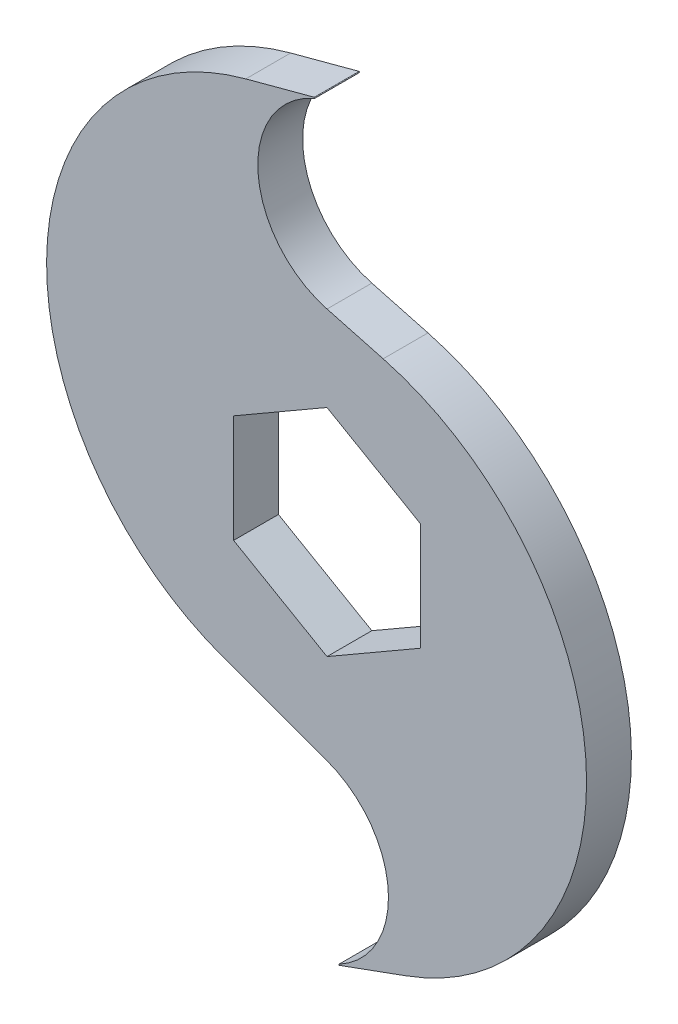
SolidWorks part; units mm, degrees
ref_plane "Front Plane" through (0, 0, 0) normal (0, 0, 1) x (1, 0, 0)
ref_plane "Top Plane" through (0, 0, 0) normal (0, 1, 0) x (1, 0, 0)
ref_plane "Right Plane" through (0, 0, 0) normal (1, 0, 0) x (0, 0, -1)
sketch "Sketch1" plane through (0, 0, 0) normal (0, 0, 1) x (1, 0, 0)
  line L0 (0, 50.8) -> (-11.0405, 47.8417)
  line L1 (0, 50.8) -> (0, 0) construction
  line L2 (0, -50.8) -> (10.7407, -46.8907)
  line L3 (0, 0) -> (0, -50.8) construction
  line L5 (0, 14.6647) -> (-12.7, 7.3323)
  line L6 (-12.7, 7.3323) -> (-12.7, -7.3323)
  line L7 (-12.7, -7.3323) -> (0, -14.6647)
  line L8 (0, -14.6647) -> (12.7, -7.3323)
  line L9 (12.7, -7.3323) -> (12.7, 7.3323)
  line L10 (12.7, 7.3323) -> (0, 14.6647)
  line L11 (0, 26.2655) -> (7.636, 24.2194)
  line L12 (0, -26.9318) -> (-14.0814, -21.8066)
  circle A0 centre (0, 0) radius 50.8 construction
  arc A1 (0, 50.8) -> (0, 26.2655) centre (3.287, 38.5327) ccw
  arc A3 (0, -50.8) -> (0, -26.9318) centre (-4.3437, -38.8659) ccw
  arc A4 (10.7407, -46.8907) -> (7.636, 24.2194) centre (-2.0222, -11.8251) ccw
  arc A5 (-11.0405, 47.8417) -> (-14.0814, -21.8066) centre (-1.581, 12.5382) ccw
  circle A6 centre (0, 0) radius 12.7 construction
  dimension "D4" = 70
  dimension "D5" = 25.4
  dimension "D1" = 101.6
  dimension "D6" = 12.7
  dimension "D2" = 11.43
  dimension "D3" = 75
extrude "Boss-Extrude1" add sketch "Sketch1" along normal mid plane 6.096
fillet "Fillet1" radius 0.0635 2 edges at (0, 50.8, 0) (0, -50.8, 0)
